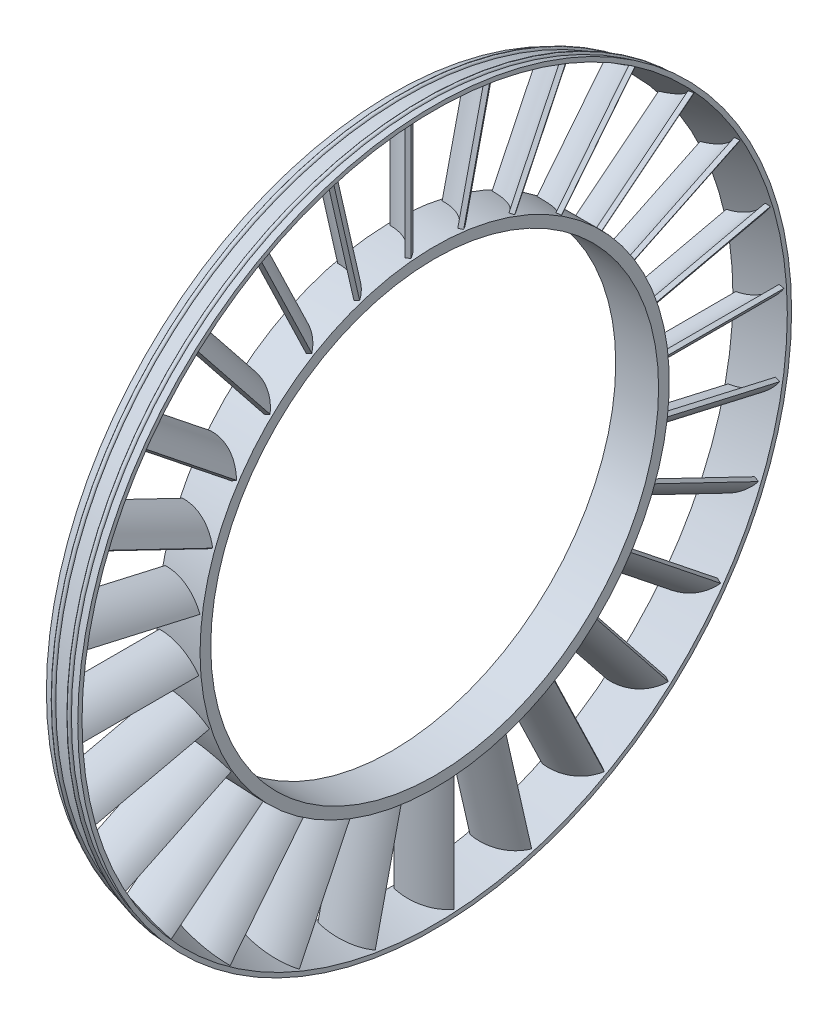
SolidWorks part; units mm, degrees
ref_plane "Front Plane" through (0, 0, 0) normal (0, 0, 1) x (1, 0, 0)
ref_plane "Top Plane" through (0, 0, 0) normal (0, 1, 0) x (1, 0, 0)
ref_plane "Right Plane" through (0, 0, 0) normal (1, 0, 0) x (0, 0, -1)
sketch "Sketch1" plane through (0, 0, 0) normal (0, 0, 1) x (1, 0, 0)
  line L0 (-19.0306, 0) -> (23.7245, 0) construction
  line L1 (0, 0) -> (0, 259.0673) construction
  line L2 (-10, 109.5) -> (-10, 298.7417) construction
  line L3 (-10, 104.5) -> (10, 104.5)
  line L4 (-10, 104.5) -> (-10, 109.5)
  line L5 (-10, 109.5) -> (10, 109.5)
  line L6 (10, 104.5) -> (10, 109.5)
  line L7 (-10, 104.5) -> (10, 109.5) construction
  line L8 (-10, 109.5) -> (10, 104.5) construction
  line L9 (10, 109.5) -> (10, 298.7417) construction
  line L10 (-10, 159.2) -> (10, 164.57)
  line L11 (-10, 161.2) -> (-5.9658, 162.2832)
  line L12 (10, 166.57) -> (10, 164.57)
  line L13 (-10, 161.2) -> (-10, 159.2)
  line L14 (-4.0342, 162.8018) -> (4.0342, 164.9682)
  line L15 (5.9658, 165.4868) -> (10, 166.57)
  arc A0 (5.9658, 165.4868) -> (4.0342, 164.9682) centre (5, 165.2275) ccw
  arc A1 (-4.0342, 162.8018) -> (-5.9658, 162.2832) centre (-5, 162.5425) ccw
  point P5 (0, 107)
  point P17 (0, 161.885)
  dimension "D7" = 2
  dimension "D8" = 2
  dimension "D1" = 5
  dimension "D2" = 20
  dimension "D3" = 104.5
  dimension "D4" = 159.2
  dimension "D5" = 164.57
  dimension "D9" = 5
  dimension "D10" = 5
sketch "Sketch2" plane through (0, 0, 0) normal (0, 0, 1) x (1, 0, 0)
  line L0 (-10, 161.2) -> (-5.9658, 162.2832) construction
  circle A0 centre (-6.8915, 162.0346) radius 1.1921
revolve "Revolve1" add sketch "Sketch1" angle 360 about L0
sketch "Sketch3" plane through (0, 0, 0) normal (0, 1, 0) x (1, 0, 0)
  line L0 (-21.0694, 0) -> (28.3313, 0) construction
  line L1 (-10, 161.2) -> (-10, -161.2) construction
  line L2 (10, -166.57) -> (10, 166.57) construction
  arc A0 (-9, 0) -> (9, -10) centre (-8.3544, -20.0379) cw
  point P3 (-9, 0)
  point P4 (9, -10)
  dimension "D1" = 1
  dimension "D2" = 1
  dimension "D3" = 10
extrude "Extrude-Thin1" add sketch "Sketch3" along normal up to surface (159.4733 mm away) thin up to face at (10, 0, 164.57) thin type one direction wall 2
pattern_circular "CirPattern1" count 28 over 360 about axis through (-19.0306, 0, 0) along (-1, 0, 0) of "Extrude-Thin1" reverse direction yes
sketch "Sketch4" plane through (0, 0, 0) normal (1, 0, 0) x (0, 0, -1)
  circle A0 centre (0, 0) radius 104.5
extrude "Cut-Extrude1" cut sketch "Sketch4" against normal mid plane 40
